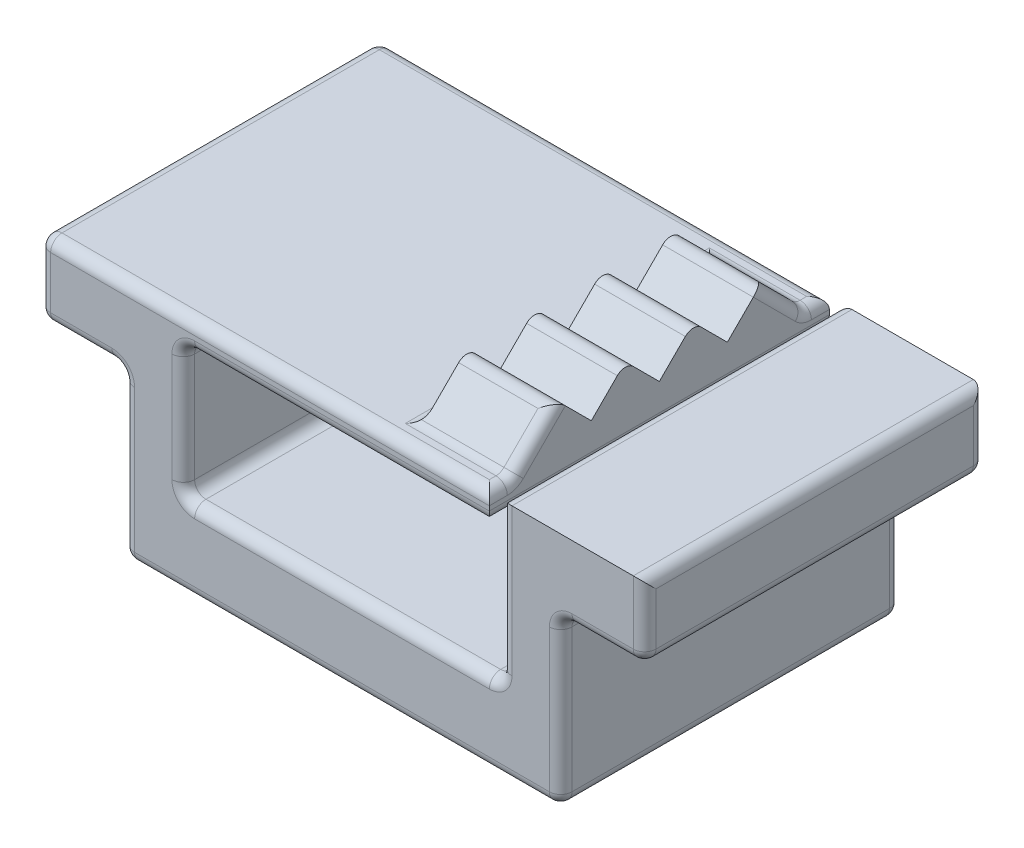
SolidWorks part; units mm, degrees
ref_plane "Front Plane" through (0, 0, 0) normal (0, 0, 1) x (1, 0, 0)
ref_plane "Top Plane" through (0, 0, 0) normal (0, 1, 0) x (1, 0, 0)
ref_plane "Right Plane" through (0, 0, 0) normal (1, 0, 0) x (0, 0, -1)
sketch "Sketch2" plane through (0, 0, 0) normal (0, 0, 1) x (1, 0, 0)
  line L0 (-72.3213, 72.576) -> (-72.3213, 68.976)
  line L1 (-53.0213, 72.576) -> (-53.0213, 68.976)
  line L3 (-72.3213, 72.576) -> (-53.0213, 72.576)
  line L5 (-72.3213, 68.976) -> (-53.0213, 68.976)
  line L8 (-53.0213, 72.576) -> (-53.0213, 76.276)
  line L9 (-53.0213, 76.276) -> (-49.3213, 76.276)
  line L10 (-49.3213, 76.276) -> (-49.3213, 79.576)
  line L11 (-49.3213, 79.576) -> (-76.0213, 79.576)
  line L12 (-62.6713, 57.576) -> (-62.6713, 72.576) construction
  line L13 (-72.3213, 72.576) -> (-72.3213, 76.276)
  line L14 (-72.3213, 76.276) -> (-76.0213, 76.276)
  line L15 (-76.0213, 76.276) -> (-76.0213, 79.576)
  point P6 (-62.6713, 79.576)
  point P21 (-62.6713, 72.576)
  point P24 (-62.6713, 68.976)
  dimension "D1" = 3.7
  dimension "D2" = 3.7
  dimension "D3" = 3.3
  dimension "D4" = 3.6
extrude "Boss-Extrude1" add sketch "Sketch2" along normal blind 15 contours L15 L14 L13 L3 L8 L9 L10 L11 | L12 L5 L1 L3 | L5 L12 L3 L0
sketch "Sketch4" plane through (0, 0, 0) normal (0, 0, -1) x (-1, 0, 0)
  line L1 (69.6713, 72.576) -> (55.6713, 72.576)
  line L2 (69.6713, 72.576) -> (69.6713, 79.576)
  line L3 (69.6713, 79.576) -> (55.6713, 79.576)
  line L4 (55.6713, 72.576) -> (55.6713, 79.576)
  line L5 (62.6713, 57.576) -> (62.6713, 72.576) construction
  line L6 (49.3213, 79.576) -> (76.0213, 79.576) construction
  point P6 (62.6713, 72.576)
  dimension "D1" = 14
  dimension "D2" = 7
extrude "Cut-Extrude1" cut sketch "Sketch4" against normal through all
sketch "Sketch5" plane through (0, 79.576, 0) normal (0, 1, 0) x (1, 0, 0)
  line L1 (-69.6713, 0) -> (-56.1713, 0)
  line L2 (-69.6713, 0) -> (-69.6713, -15)
  line L3 (-69.6713, -15) -> (-56.1713, -15)
  line L4 (-56.1713, 0) -> (-56.1713, -15)
  line L6 (-69.6713, -15) -> (-76.0213, -15) construction
  dimension "D1" = 13.5
extrude "Boss-Extrude2" add sketch "Sketch5" against normal blind 1.2
sketch "Sketch6" plane through (-56.1713, 0, 0) normal (1, 0, 0) x (0, 0, -1)
  line L0 (-10.5, 80.076) -> (-12, 81.576)
  line L1 (-12, 81.576) -> (-13.5, 80.076)
  line L2 (-10.5, 80.076) -> (-13.5, 80.076)
  line L3 (-10.5, 80.076) -> (-10.5, 79.576)
  line L4 (-10.5, 79.576) -> (-13.5, 79.576)
  line L5 (-13.5, 79.576) -> (-13.5, 80.076)
  line L6 (-15, 79.576) -> (0, 79.576) construction
  point P7 (-13.5, 79.826)
  line M2 (0, 79.576) -> (-15, 79.576)
  dimension "D1" = 45
  dimension "D2" = 45
  dimension "D3" = 1.5
  dimension "D4" = 0.5
  dimension "D5" = 1.5
extrude "Boss-Extrude3" add sketch "Sketch6" against normal blind 4 contours L5 L3 L2 M2 | L2 L0 L1
pattern_linear "LPattern1" count 4 spacing 3 along (0, 0, -1) of "Boss-Extrude3"
sketch "Sketch7" plane through (-56.1713, 0, 0) normal (1, 0, 0) x (0, 0, -1)
  line L0 (-13.5, 80.076) -> (-13.5, 79.576)
  line L1 (-13.5, 79.576) -> (-14, 79.576)
  line L2 (-15, 79.576) -> (-13.5, 79.576) construction
  line L3 (-14, 79.576) -> (-13.5, 80.076)
  line L4 (-1.5, 80.076) -> (-1.5, 79.576)
  line L5 (-1.5, 80.076) -> (-1.5, 79.576) construction
  line L6 (-1.5, 79.576) -> (0, 79.576) construction
  line L7 (-1.5, 79.576) -> (-1, 79.576)
  line L8 (-1, 79.576) -> (-1.5, 80.076)
  line L9 (-1.5, 80.076) -> (-1.5126, 80.0721)
  line L10 (-12, 81.576) -> (-13.5, 80.076) construction
  line L11 (-1.5, 80.076) -> (-3, 81.576) construction
extrude "Boss-Extrude4" add sketch "Sketch7" against normal blind 4 contours L4 L7 L8 | L3 L0 L1
fillet "Fillet1" radius 0.5 46 edges at (-58.1713, 79.576, 1) (-51.1713, 76.276, 0) (-53.0213, 72.626, 0) (-58.1713, 79.576, 14) (-62.6713, 68.976, 0) (-72.3213, 72.626, 15) (-72.3213, 72.626, 0) (-74.1713, 76.276, 0) (-76.0213, 77.926, 0) (-76.0213, 79.576, 7.5) (-49.3213, 79.576, 7.5) (-49.3213, 76.276, 7.5) (-53.0213, 76.276, 7.5) (-53.0213, 68.976, 7.5) (-72.3213, 68.976, 7.5) (-72.3213, 76.276, 7.5) (-76.0213, 76.276, 7.5) (-62.6713, 68.976, 15) (-53.0213, 72.626, 15) (-51.1713, 76.276, 15) (-49.3213, 77.926, 15) (-69.6713, 75.476, 15) (-62.6713, 72.576, 15) (-69.6713, 72.576, 7.5) (-55.6713, 76.076, 15) (-55.6713, 72.576, 7.5) (-55.6713, 79.576, 7.5) (-69.6713, 75.476, 0) (-55.6713, 76.076, 0) (-62.6713, 72.576, 0) (-76.0213, 77.926, 15) (-69.6713, 78.376, 7.5) (-62.9213, 78.376, 0) (-56.1713, 78.376, 7.5) (-62.9213, 78.376, 15) (-56.1713, 79.576, 14.5) (-58.1713, 81.576, 12) (-60.1713, 79.576, 7.5) (-56.1713, 80.576, 13) (-58.1713, 81.576, 9) (-56.1713, 80.576, 2) (-74.1713, 76.276, 15) (-58.1713, 81.576, 6) (-58.1713, 81.576, 3) (-49.3213, 77.926, 0) (-56.1713, 79.576, 0.5)
